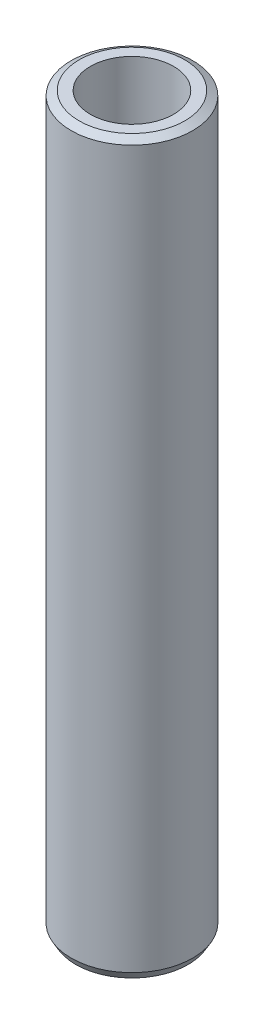
SolidWorks part; units mm, degrees
ref_plane "Front Plane" through (0, 0, 0) normal (0, 0, 1) x (1, 0, 0)
ref_plane "Top Plane" through (0, 0, 0) normal (0, 1, 0) x (1, 0, 0)
ref_plane "Right Plane" through (0, 0, 0) normal (1, 0, 0) x (0, 0, -1)
sketch "Sketch1" plane through (0, 0, 0) normal (0, 1, 0) x (1, 0, 0)
  circle A0 centre (0, 0) radius 50
  dimension "SHAFT_OD" = 100
extrude "Boss-Extrude1" add sketch "Sketch1" along normal blind 600
sketch "Sketch2" plane through (0, 0, 0) normal (0, 1, 0) x (1, 0, 0)
  circle A0 centre (0, 0) radius 34.247
  dimension "BORE_D" = 68.4941
extrude "Cut-Extrude1" cut sketch "Sketch2" along normal through all
chamfer "Chamfer1" distance 3.7395 angle 60 2 edges at (0, 600, 50) (0, 0, 50) first distance on face at (0, 600, 50) first distance on face at (0, 0, 34.247)
